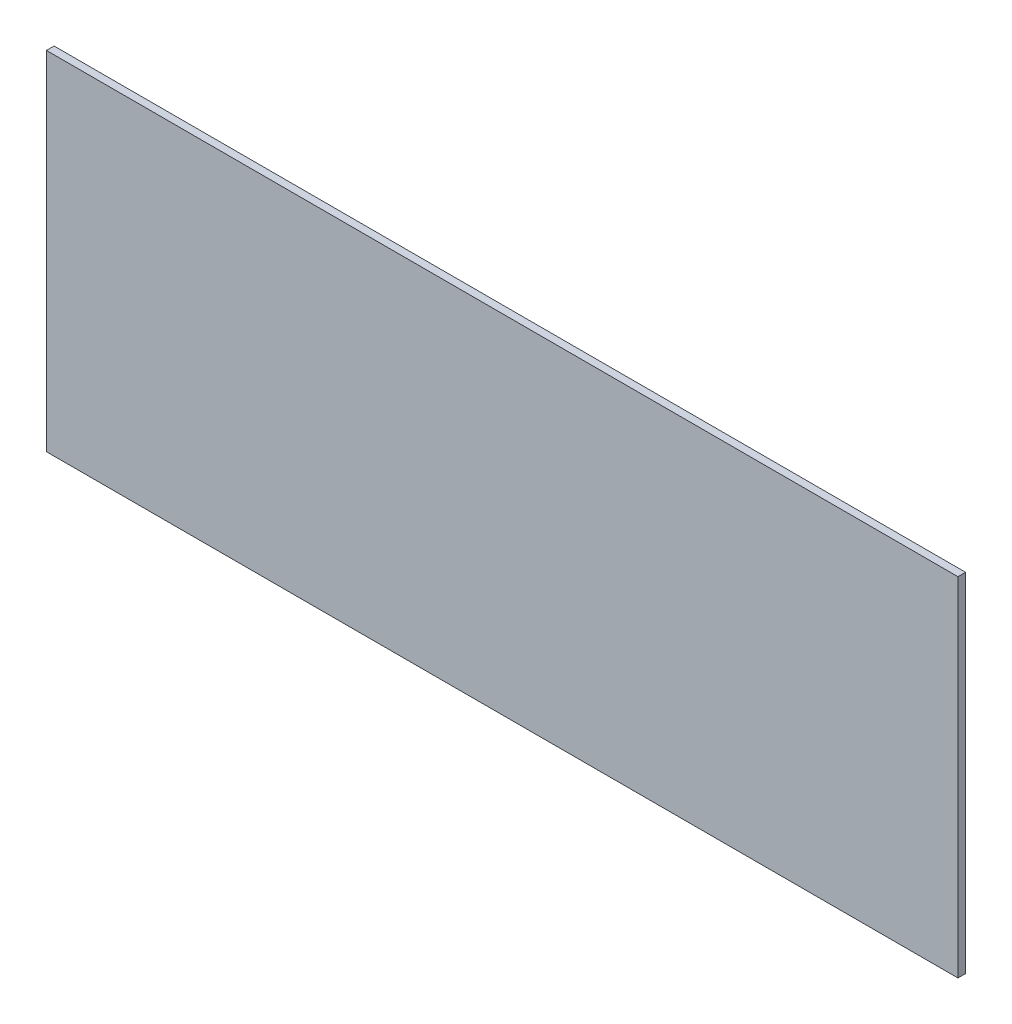
SolidWorks part; units mm, degrees
ref_plane "Front Plane" through (0, 0, 0) normal (0, 0, 1) x (1, 0, 0)
ref_plane "Top Plane" through (0, 0, 0) normal (0, 1, 0) x (1, 0, 0)
ref_plane "Right Plane" through (0, 0, 0) normal (1, 0, 0) x (0, 0, -1)
sketch "Sketch1" plane through (0, 0, 0) normal (0, 0, 1) x (1, 0, 0)
  line L0 (223.7, 24.5) -> (223.7, -237.7) construction
  line L1 (-169.7, 24.5) -> (223.7, 24.5)
  line L2 (-169.7, 24.5) -> (-169.7, -125.5)
  line L3 (-169.7, -125.5) -> (223.7, -125.5)
  line L4 (223.7, 24.5) -> (223.7, -125.5)
  line L5 (-169.7, 24.5) -> (223.7, -125.5) construction
  line L6 (-169.7, -125.5) -> (223.7, 24.5) construction
  line L7 (-169.7, -237.7) -> (-169.7, 24.5) construction
  line L8 (-173, 24.5) -> (227, 24.5) construction
  point P4 (27, -50.5)
  dimension "D1" = 150
extrude "Boss-Extrude1" add sketch "Sketch1" along normal blind 3.3
